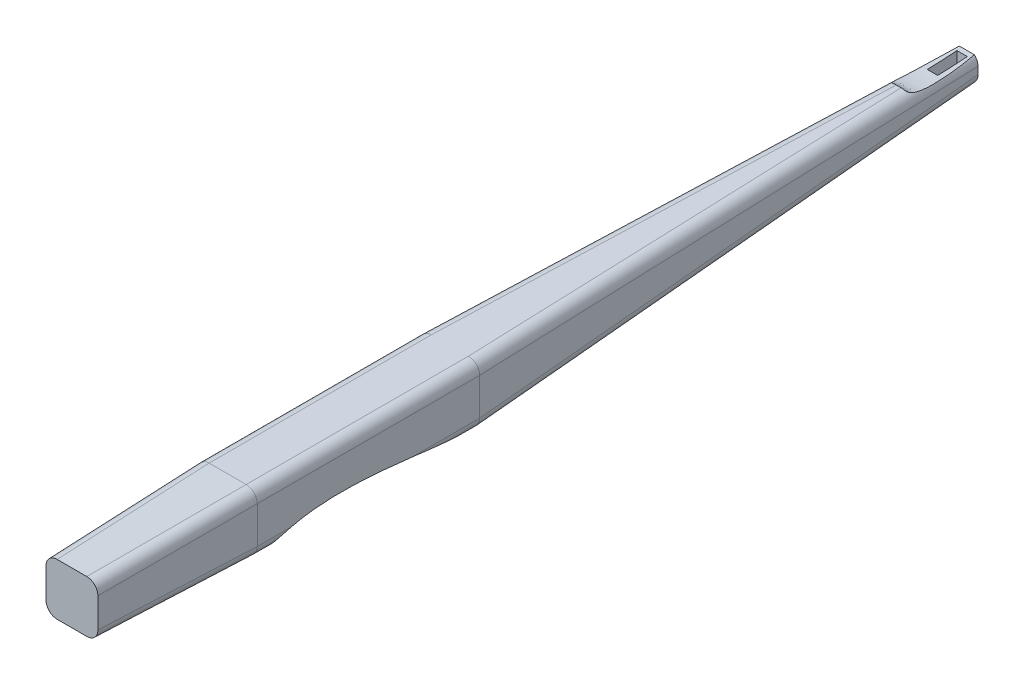
SolidWorks part; units mm, degrees
ref_plane "Front Plane" through (0, 0, 0) normal (0, 0, 1) x (1, 0, 0)
ref_plane "Top Plane" through (0, 0, 0) normal (0, 1, 0) x (1, 0, 0)
ref_plane "Right Plane" through (0, 0, 0) normal (1, 0, 0) x (0, 0, -1)
sketch "Sketch1" plane through (0, 0, 0) normal (0, 0, 1) x (1, 0, 0)
  line L1 (50.8, -50.8) -> (-50.8, -50.8)
  line L2 (50.8, -50.8) -> (50.8, 50.8)
  line L3 (50.8, 50.8) -> (-50.8, 50.8)
  line L4 (-50.8, -50.8) -> (-50.8, 50.8)
  line L5 (50.8, -50.8) -> (-50.8, 50.8) construction
  line L6 (50.8, 50.8) -> (-50.8, -50.8) construction
  point P0 (0, 0)
  dimension "D1" = 101.6
extrude "Boss-Extrude1" add sketch "Sketch1" against normal blind 381
ref_plane "Plane1" through (0, 0, -1266.444) normal (0, 0, -1) x (-1, 0, 0)
sketch "Sketch2" plane through (0, 0, -1266.444) normal (0, 0, -1) x (-1, 0, 0)
  line L0 (-50.8, 50.8) -> (50.8, 50.8) construction
  line L1 (19.05, 0) -> (-19.05, 0)
  line L2 (19.05, 0) -> (19.05, 50.8)
  line L3 (19.05, 50.8) -> (-19.05, 50.8)
  line L4 (-19.05, 0) -> (-19.05, 50.8)
  line L5 (19.05, 0) -> (-19.05, 50.8) construction
  line L6 (19.05, 50.8) -> (-19.05, 0) construction
  line L7 (-50.8, 50.8) -> (50.8, 50.8) construction
  line L8 (0, 0) -> (0, 58.6794) construction
  point P6 (0, 25.4)
  dimension "D1" = 50.8
  dimension "D2" = 38.1
loft "Loft1" add profiles "Sketch2" section face at (0, 0, -381) section "Sketch2" connector at (50.8, 50.8, -381) connector at (19.05, 50.8, -1266.444)
ref_plane "Plane2" through (0, 0, 266.7) normal (0, 0, 1) x (1, 0, 0)
sketch "Sketch4" plane through (0, 0, 266.7) normal (0, 0, 1) x (1, 0, 0)
  line L1 (44.45, -44.45) -> (-44.45, -44.45)
  line L2 (44.45, -44.45) -> (44.45, 44.45)
  line L3 (44.45, 44.45) -> (-44.45, 44.45)
  line L4 (-44.45, -44.45) -> (-44.45, 44.45)
  line L5 (44.45, -44.45) -> (-44.45, 44.45) construction
  line L6 (44.45, 44.45) -> (-44.45, -44.45) construction
  point P0 (0, 0)
  dimension "D1" = 88.9
loft "Loft2" add profiles "Sketch4" section face at (0, 0, 0) section "Sketch4" connector at (50.8, 50.8, 0) connector at (44.45, 44.45, 266.7)
curve "Curve1"
  spline degree 3 poles (0, 25.4, 0.0064) (0, 25.2657, 0.0346) (0, 24.9974, 0.0911) (0, 24.5944, 0.1721) (0, 24.1917, 0.2509) (0, 23.7893, 0.3278) (0, 23.3874, 0.4029) (0, 22.9859, 0.4765) (0, 22.5851, 0.5485) (0, 22.1849, 0.619) (0, 21.7856, 0.688) (0, 21.3872, 0.7554) (0, 20.9898, 0.8212) (0, 20.5935, 0.8853) (0, 20.1985, 0.9476) (0, 19.8047, 1.0082) (0, 19.4123, 1.067) (0, 19.0215, 1.124) (0, 18.6322, 1.1792) (0, 18.2447, 1.2326) (0, 17.859, 1.2841) (0, 17.4751, 1.3339) (0, 17.0933, 1.382) (0, 16.7135, 1.4283) (0, 16.3359, 1.4729) (0, 15.9606, 1.5158) (0, 15.5877, 1.5571) (0, 15.2173, 1.5967) (0, 14.8494, 1.6346) (0, 14.4842, 1.6709) (0, 14.1217, 1.7054) (0, 13.7621, 1.7383) (0, 13.4054, 1.7695) (0, 13.0517, 1.7989) (0, 12.7011, 1.8265) (0, 12.3537, 1.8522) (0, 12.0097, 1.8761) (0, 11.6689, 1.8981) (0, 11.3317, 1.918) (0, 10.9979, 1.936) (0, 10.6678, 1.9519) (0, 10.3414, 1.9657) (0, 10.0188, 1.9774) (0, 9.7001, 1.9869) (0, 9.3853, 1.9942) (0, 9.0746, 1.9993) (0, 8.7679, 2.0022) (0, 8.4655, 2.0029) (0, 8.1673, 2.0014) (0, 7.8734, 1.9977) (0, 7.584, 1.9918) (0, 7.2991, 1.9837) (0, 7.0187, 1.9735) (0, 6.7429, 1.9612) (0, 6.4718, 1.9468) (0, 6.2055, 1.9304) (0, 5.944, 1.912) (0, 5.6874, 1.8917) (0, 5.4358, 1.8694) (0, 5.1892, 1.8454) (0, 4.9477, 1.8195) (0, 4.7114, 1.792) (0, 4.4802, 1.7628) (0, 4.2543, 1.7319) (0, 4.0338, 1.6995) (0, 3.8186, 1.6656) (0, 3.6089, 1.6303) (0, 3.4046, 1.5936) (0, 3.2059, 1.5556) (0, 3.0127, 1.5163) (0, 2.8252, 1.4759) (0, 2.6434, 1.4343) (0, 2.4673, 1.3917) (0, 2.297, 1.3481) (0, 2.1325, 1.3035) (0, 1.9738, 1.2581) (0, 1.8211, 1.2119) (0, 1.6742, 1.1649) (0, 1.5334, 1.1173) (0, 1.3985, 1.0691) (0, 1.2697, 1.0204) (0, 1.147, 0.9712) (0, 1.0304, 0.9215) (0, 0.9199, 0.8715) (0, 0.8155, 0.8212) (0, 0.7173, 0.7706) (0, 0.6254, 0.7198) (0, 0.5396, 0.6689) (0, 0.4601, 0.6178) (0, 0.3869, 0.5666) (0, 0.3199, 0.5153) (0, 0.2592, 0.4639) (0, 0.2049, 0.4126) (0, 0.1568, 0.3611) (0, 0.1151, 0.3097) (0, 0.0797, 0.2582) (0, 0.0507, 0.2067) (0, 0.0281, 0.1551) (0, 0.0119, 0.1034) (0, 0.0022, 0.0517) (0, -0.0011, 0.0014) (0, 0.0021, -0.0476) (0, 0.0119, -0.095) (0, 0.0281, -0.1421) (0, 0.0507, -0.1886) (0, 0.0797, -0.2345) (0, 0.1151, -0.2796) (0, 0.1568, -0.3238) (0, 0.2049, -0.3671) (0, 0.2593, -0.4092) (0, 0.32, -0.4502) (0, 0.387, -0.49) (0, 0.4602, -0.5285) (0, 0.5397, -0.5656) (0, 0.6255, -0.6013) (0, 0.7175, -0.6357) (0, 0.8157, -0.6686) (0, 0.92, -0.7001) (0, 1.0306, -0.7301) (0, 1.1472, -0.7588) (0, 1.2699, -0.786) (0, 1.3988, -0.8119) (0, 1.5336, -0.8364) (0, 1.6745, -0.8596) (0, 1.8213, -0.8815) (0, 1.974, -0.9021) (0, 2.1327, -0.9215) (0, 2.2972, -0.9397) (0, 2.4675, -0.9567) (0, 2.6436, -0.9725) (0, 2.8254, -0.9871) (0, 3.0129, -1.0006) (0, 3.206, -1.0129) (0, 3.4048, -1.0241) (0, 3.609, -1.0341) (0, 3.8188, -1.043) (0, 4.0339, -1.0507) (0, 4.2545, -1.0573) (0, 4.4804, -1.0628) (0, 4.7115, -1.0671) (0, 4.9478, -1.0703) (0, 5.1893, -1.0723) (0, 5.4359, -1.0732) (0, 5.6875, -1.073) (0, 5.9441, -1.0718) (0, 6.2056, -1.0694) (0, 6.4719, -1.0661) (0, 6.7429, -1.0617) (0, 7.0187, -1.0564) (0, 7.2991, -1.0502) (0, 7.584, -1.0431) (0, 7.8735, -1.0352) (0, 8.1673, -1.0265) (0, 8.4655, -1.017) (0, 8.7679, -1.0069) (0, 9.0746, -0.996) (0, 9.3853, -0.9846) (0, 9.7001, -0.9725) (0, 10.0188, -0.9599) (0, 10.3414, -0.9466) (0, 10.6678, -0.9328) (0, 10.9979, -0.9185) (0, 11.3316, -0.9035) (0, 11.6689, -0.888) (0, 12.0096, -0.8718) (0, 12.3537, -0.855) (0, 12.7011, -0.8375) (0, 13.0517, -0.8194) (0, 13.4053, -0.8005) (0, 13.762, -0.781) (0, 14.1217, -0.7608) (0, 14.4841, -0.7398) (0, 14.8494, -0.7181) (0, 15.2172, -0.6958) (0, 15.5877, -0.6729) (0, 15.9606, -0.6493) (0, 16.3359, -0.6253) (0, 16.7134, -0.6007) (0, 17.0932, -0.5758) (0, 17.475, -0.5506) (0, 17.8589, -0.5252) (0, 18.2446, -0.4996) (0, 18.6321, -0.4739) (0, 19.0214, -0.4481) (0, 19.4122, -0.4224) (0, 19.8046, -0.3966) (0, 20.1983, -0.3708) (0, 20.5934, -0.3449) (0, 20.9897, -0.3189) (0, 21.3871, -0.2926) (0, 21.7855, -0.2659) (0, 22.1848, -0.2386) (0, 22.585, -0.2108) (0, 22.9858, -0.1822) (0, 23.3872, -0.153) (0, 23.7892, -0.1231) (0, 24.1915, -0.0928) (0, 24.5941, -0.0626) (0, 24.997, -0.0331) (0, 25.2657, -0.0153) (0, 25.4, -0.0064) knots 0 0 0 0 0.007941 0.015868 0.023782 0.031684 0.039571 0.047444 0.055299 0.063136 0.070953 0.078747 0.086517 0.09426 0.101975 0.10966 0.117312 0.124931 0.132515 0.14006 0.147567 0.155033 0.162457 0.169836 0.17717 0.184456 0.191693 0.198879 0.206013 0.213092 0.220115 0.227081 0.233988 0.240834 0.247617 0.254336 0.260989 0.267575 0.274092 0.280538 0.286913 0.293214 0.299441 0.305592 0.311665 0.31766 0.323575 0.329409 0.33516 0.340829 0.346413 0.351912 0.357324 0.362648 0.367884 0.373031 0.378086 0.383051 0.387923 0.392702 0.397387 0.401977 0.406471 0.410868 0.415168 0.41937 0.423472 0.427475 0.431378 0.435179 0.438879 0.442477 0.445971 0.449362 0.45265 0.455833 0.458911 0.461884 0.464751 0.467513 0.470169 0.47272 0.475165 0.477504 0.479738 0.481867 0.483893 0.485816 0.487638 0.48936 0.490986 0.492517 0.493957 0.495311 0.496586 0.497786 0.498922 0.500002 0.50104 0.502047 0.503039 0.503952 0.504878 0.505831 0.506824 0.507866 0.508967 0.510136 0.51138 0.512704 0.514115 0.515615 0.517209 0.518901 0.520691 0.522584 0.524581 0.526682 0.528891 0.531207 0.533632 0.536166 0.538809 0.541562 0.544425 0.547398 0.550481 0.553673 0.556974 0.560384 0.563903 0.567529 0.571261 0.5751 0.579045 0.583094 0.587247 0.591503 0.595862 0.600321 0.60488 0.609539 0.614295 0.619148 0.624097 0.629141 0.634278 0.639507 0.644828 0.650237 0.655735 0.66132 0.666991 0.672745 0.678583 0.684501 0.690499 0.696575 0.702728 0.708956 0.715257 0.72163 0.728074 0.734587 0.741166 0.747811 0.75452 0.761292 0.768124 0.775014 0.781962 0.788966 0.796023 0.803132 0.810291 0.817498 0.824752 0.832051 0.839391 0.846773 0.854193 0.86165 0.869142 0.876666 0.884222 0.891806 0.899418 0.907055 0.914715 0.922398 0.9301 0.93782 0.945557 0.953308 0.961072 0.968847 0.97663 0.984418 0.99221 1 1 1 1
fillet "Fillet1" radius 19.05 12 edges at (-50.8, -50.8, -190.5) (50.8, -50.8, -190.5) (-50.8, 50.8, -190.5) (50.8, 50.8, -190.5)
curve "Curve3"
  spline degree 3 poles (2540, 2.667, 0) (2497.673, 7.5246, 0) (2413.0485, 17.2363, 0) (2243.7542, 35.2824, 0) (2032.1327, 56.0234, 0) (1778.1166, 78.0043, 0) (1524.1217, 97.1783, 0) (1270.1207, 112.8101, 0) (1016.1031, 123.9325, 0) (804.3443, 127.823, 0) (634.9677, 126.2841, 0) (507.9066, 122.1048, 0) (380.755, 114.0399, 0) (274.8766, 102.8064, 0) (190.1483, 89.339, 0) (126.4668, 76.1883, 0) (72.3226, 59.4798, 0) (27.4187, 40.5773, 0) (-16.236, 0, 0) (27.4187, -40.5773, 0) (72.3226, -59.4798, 0) (126.4668, -76.1883, 0) (190.1483, -89.339, 0) (274.8766, -102.8064, 0) (380.755, -114.0399, 0) (507.9066, -122.1048, 0) (634.9677, -126.2841, 0) (804.3443, -127.823, 0) (1016.1031, -123.9325, 0) (1270.1207, -112.8101, 0) (1524.1217, -97.1783, 0) (1778.1166, -78.0043, 0) (2032.1327, -56.0234, 0) (2243.7542, -35.2824, 0) (2413.0485, -17.2363, 0) (2497.673, -7.5246, 0) (2540, -2.667, 0) knots 0 0 0 0 0.024824 0.04963 0.099197 0.148713 0.198182 0.247604 0.29698 0.346318 0.370984 0.395664 0.420382 0.445198 0.457689 0.470304 0.483229 0.490069 0.5 0.509931 0.516771 0.529696 0.542311 0.554802 0.579618 0.604336 0.629016 0.653682 0.70302 0.752396 0.801818 0.851287 0.900803 0.95037 0.975176 1 1 1 1
sketch "Sketch5" plane through (50.8, 0, 0) normal (1, 0, 0) x (0, 0, -1)
  line L0 (381, -50.7277) -> (381, -50.9055)
  line L1 (381, -50.8166) -> (25.4, -50.8) construction
  line L2 (25.4, -88.4118) -> (25.4, -13.1882) construction
  line L3 (381, -50.8) -> (0, -50.8) construction
  line L4 (381, -50.8) -> (0, -50.8) construction
  line L5 (0, -31.75) -> (0, 31.75) construction
  line L6 (0, -31.75) -> (0, 31.75) construction
  spline S1 degree 3 poles (381, -50.7277) (379.1199, -50.3321) (375.363, -49.5414) (369.7215, -48.4078) (364.0838, -47.3036) (358.4505, -46.2278) (352.823, -45.1759) (347.2027, -44.1462) (339.7295, -42.8033) (328.5708, -40.8557) (315.5949, -38.7062) (302.6904, -36.6942) (291.728, -35.0732) (277.3081, -33.0583) (263.0217, -31.2328) (248.8856, -29.5892) (238.481, -28.4574) (228.2201, -27.4186) (218.113, -26.4737) (208.17, -25.6253) (198.4009, -24.8773) (187.2768, -24.1315) (174.893, -23.4607) (161.3521, -22.9658) (148.3082, -22.7457) (135.7909, -22.8044) (125.0735, -23.1035) (116.0693, -23.5418) (108.6813, -24.0278) (101.5674, -24.6223) (94.7349, -25.3194) (88.1906, -26.1131) (81.941, -26.9969) (75.9925, -27.9642) (70.351, -29.0084) (65.0221, -30.1224) (60.7855, -31.1171) (56.8117, -32.1349) (53.7949, -32.973) (50.895, -33.8502) (48.8395, -34.5074) (46.8675, -35.1739) (44.9797, -35.8488) (43.1763, -36.5312) (41.458, -37.2204) (39.8251, -37.9154) (38.2779, -38.6155) (36.817, -39.32) (35.4426, -40.0281) (34.155, -40.7392) (32.9546, -41.4527) (31.8415, -42.1681) (30.8162, -42.8849) (29.8787, -43.6029) (29.0293, -44.3216) (28.2681, -45.0409) (27.5954, -45.7607) (27.0113, -46.481) (26.5161, -47.2018) (26.11, -47.9233) (25.7934, -48.6455) (25.5666, -49.3686) (25.4308, -50.0924) (25.3849, -50.7974) (25.4301, -51.483) (25.5667, -52.1467) (25.7932, -52.8055) (26.1099, -53.4571) (26.516, -54.0996) (27.0114, -54.7312) (27.5957, -55.3504) (28.2686, -55.9558) (29.03, -56.546) (29.8797, -57.12) (30.8175, -57.6766) (31.8431, -58.2152) (32.9564, -58.7349) (34.1571, -59.2353) (35.4448, -59.716) (36.8195, -60.1768) (38.2806, -60.6176) (39.8279, -61.0385) (41.4609, -61.4395) (43.1793, -61.821) (44.9827, -62.1832) (46.8706, -62.5265) (48.8425, -62.8512) (50.898, -63.1578) (53.0366, -63.4466) (55.2577, -63.718) (57.5607, -63.9724) (60.7922, -64.2944) (65.0329, -64.6528) (70.361, -65.0118) (76.0017, -65.3071) (81.9495, -65.5385) (88.1982, -65.7059) (94.7417, -65.8095) (101.5733, -65.8497) (108.6863, -65.828) (116.0733, -65.7472) (123.7271, -65.6107) (131.6398, -65.4232) (139.8036, -65.1893) (148.2102, -64.9142) (156.8512, -64.6019) (165.718, -64.2557) (174.8015, -63.8772) (187.3206, -63.3239) (200.0971, -62.7092) (213.1176, -62.0258) (223.1438, -61.4687) (233.3289, -60.872) (245.4251, -60.1294) (257.6788, -59.3414) (270.0783, -58.5241) (280.8495, -57.8088) (289.8905, -57.2098) (299.0088, -56.6089) (308.1952, -56.0068) (319.2718, -55.2812) (328.5429, -54.665) (335.9878, -54.1576) (341.5896, -53.7678) (347.2012, -53.3681) (352.8214, -52.9583) (358.4485, -52.5398) (364.0812, -52.1157) (369.7181, -51.6937) (375.3574, -51.2796) (379.1192, -51.0302) (381, -50.9055) knots 0 0 0 0 0.007941 0.015868 0.023782 0.031684 0.039571 0.047444 0.055299 0.070953 0.09426 0.10966 0.124931 0.14006 0.169836 0.184456 0.198879 0.213092 0.227081 0.240834 0.254336 0.267575 0.286913 0.305592 0.323575 0.340829 0.357324 0.367884 0.378086 0.387923 0.397387 0.406471 0.415168 0.423472 0.431378 0.438879 0.445971 0.449362 0.455833 0.458911 0.461884 0.464751 0.467513 0.470169 0.47272 0.475165 0.477504 0.479738 0.481867 0.483893 0.485816 0.487638 0.48936 0.490986 0.492517 0.493957 0.495311 0.496586 0.497786 0.498922 0.500002 0.50104 0.502047 0.503039 0.503952 0.504878 0.505831 0.506824 0.507866 0.508967 0.510136 0.51138 0.512704 0.514115 0.515615 0.517209 0.518901 0.520691 0.522584 0.524581 0.526682 0.528891 0.531207 0.533632 0.536166 0.538809 0.541562 0.544425 0.547398 0.550481 0.553673 0.556974 0.563903 0.571261 0.579045 0.587247 0.595862 0.60488 0.614295 0.624097 0.634278 0.644828 0.655735 0.666991 0.678583 0.690499 0.702728 0.715257 0.728074 0.75452 0.768124 0.781962 0.796023 0.810291 0.832051 0.846773 0.86165 0.876666 0.884222 0.899418 0.914715 0.9301 0.93782 0.945557 0.953308 0.961072 0.968847 0.97663 0.984418 0.99221 1 1 1 1
  point P7 (25.4, -50.8)
  dimension "D1" = 355.6
  dimension "D2" = 25.4
extrude "Cut-Extrude1" cut sketch "Sketch5" against normal through all
sketch "Sketch7" plane through (0, 0, 0) normal (1, 0, 0) x (0, 0, -1)
  line L0 (1315.974, 50.9747) -> (1315.974, 50.6253)
  line L1 (1315.974, 50.9747) -> (1149.6041, 50.8) construction
  line L2 (1149.6041, 207.0085) -> (1149.6041, -105.4085) construction
  line L3 (380.6586, 50.8) -> (1266.1026, 50.8) construction
  line L4 (380.6586, 50.8) -> (1215.4961, 50.8) construction
  line L5 (1266.444, 31.75) -> (1266.444, 50.8) construction
  line L6 (1266.444, 31.75) -> (1266.444, 50.8) construction
  spline S0 degree 3 poles (1315.974, 50.9747) (1313.2016, 51.2929) (1307.6587, 51.929) (1296.5699, 53.111) (1282.7087, 54.4695) (1266.0707, 55.9093) (1249.434, 57.1652) (1232.797, 58.1891) (1216.1588, 58.9176) (1202.2886, 59.1724) (1191.1945, 59.0716) (1182.872, 58.7979) (1174.5435, 58.2696) (1167.6085, 57.5338) (1162.0588, 56.6517) (1157.8877, 55.7903) (1154.3412, 54.6959) (1151.4, 53.4578) (1148.5406, 50.8) (1151.4, 48.1422) (1154.3412, 46.9041) (1157.8877, 45.8097) (1162.0588, 44.9483) (1167.6085, 44.0662) (1174.5435, 43.3304) (1182.872, 42.8021) (1191.1945, 42.5284) (1202.2886, 42.4276) (1216.1588, 42.6824) (1232.797, 43.4109) (1249.434, 44.4348) (1266.0707, 45.6907) (1282.7087, 47.1305) (1296.5699, 48.489) (1307.6587, 49.671) (1313.2016, 50.3071) (1315.974, 50.6253) knots 0 0 0 0 0.024824 0.04963 0.099197 0.148713 0.198182 0.247604 0.29698 0.346318 0.370984 0.395664 0.420382 0.445198 0.457689 0.470304 0.483229 0.490069 0.5 0.509931 0.516771 0.529696 0.542311 0.554802 0.579618 0.604336 0.629016 0.653682 0.70302 0.752396 0.801818 0.851287 0.900803 0.95037 0.975176 1 1 1 1
  point P0 (1169.3485, 50.8)
  point P6 (1149.6041, 50.8)
  point P7 (1118.1308, 77.1248)
  point P10 (0, 0)
  point P11 (0, 0)
  dimension "D1" = 166.37
  dimension "D2" = 49.53
extrude "Cut-Extrude2" cut sketch "Sketch7" against normal through all and the other way through all
sketch "Sketch8" plane through (0, 50.8, 0) normal (0, 1, 0) x (1, 0, 0)
  line L0 (0, 1266.444) -> (0, 1149.6041) construction
  line L1 (12.9134, 1266.444) -> (-12.9134, 1266.444) construction
  line L2 (-4.1774, 1149.6041) -> (4.1774, 1149.6041) construction
  line L4 (8.89, 1258.3161) -> (-8.89, 1258.3161)
  line L5 (8.89, 1258.3161) -> (8.89, 1207.5161)
  line L6 (8.89, 1207.5161) -> (-8.89, 1207.5161)
  line L7 (-8.89, 1258.3161) -> (-8.89, 1207.5161)
  line L8 (8.89, 1258.3161) -> (-8.89, 1207.5161) construction
  line L9 (8.89, 1207.5161) -> (-8.89, 1258.3161) construction
  point P2 (0, 1232.9161)
  dimension "D1" = 50.8
  dimension "D2" = 17.78
  dimension "D3" = 57.912
extrude "Cut-Extrude3" cut sketch "Sketch8" against normal blind 37.338
